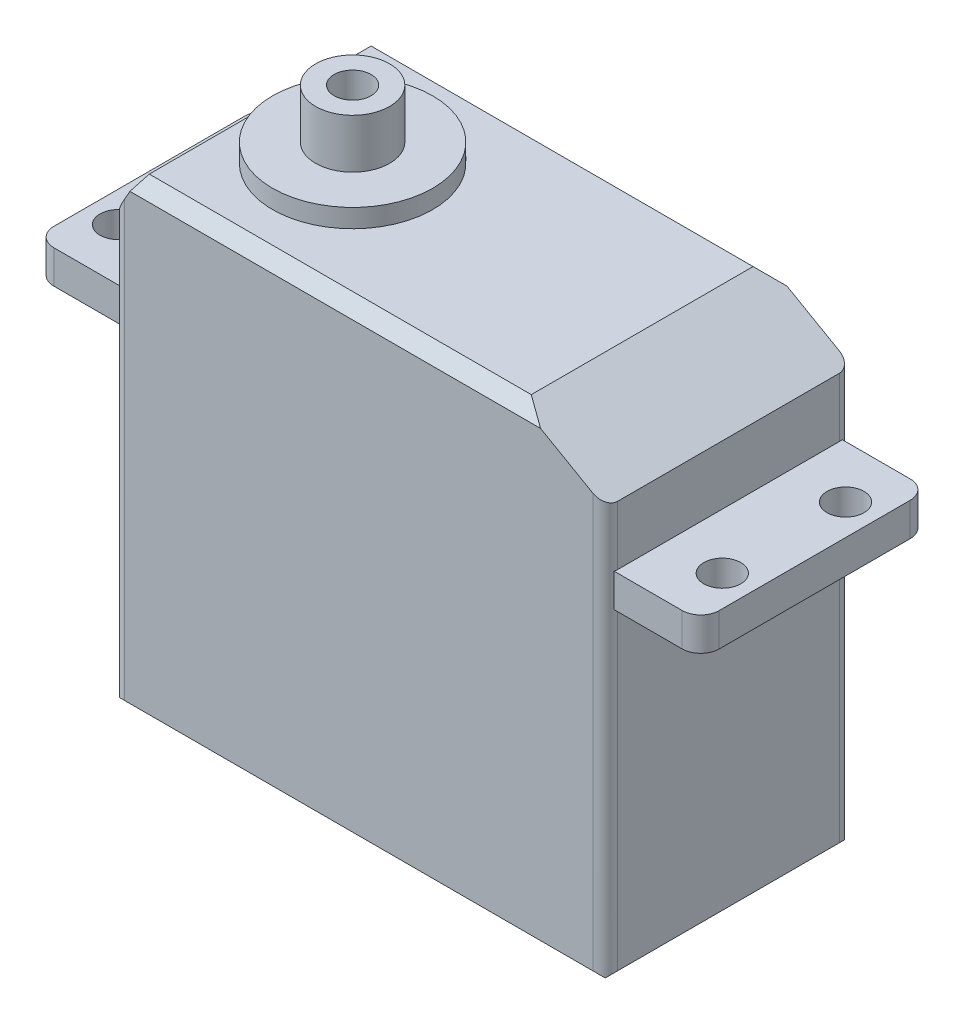
SolidWorks part; units mm, degrees
ref_plane "前视基准面" through (0, 0, 0) normal (0, 0, 1) x (1, 0, 0)
ref_plane "上视基准面" through (0, 0, 0) normal (0, 1, 0) x (1, 0, 0)
ref_plane "右视基准面" through (0, 0, 0) normal (1, 0, 0) x (0, 0, -1)
sketch "草图1" plane through (0, 0, 0) normal (0, 0, 1) x (1, 0, 0)
  line L1 (0, 0) -> (40, 0)
  line L2 (0, 0) -> (0, 38)
  line L3 (0, 38) -> (40, 38)
  line L4 (40, 0) -> (40, 38)
  dimension "D1" = 40
  dimension "D2" = 38
extrude "凸台-拉伸1" add sketch "草图1" along normal blind 20
sketch "草图2" plane through (0, 0, 0) normal (-1, 0, 0) x (0, 0, 1)
  line L0 (20, 0) -> (0, 0) construction
  line L1 (0.75, 29.2) -> (19.25, 29.2)
  line L2 (0.75, 29.2) -> (0.75, 26.5)
  line L3 (0.75, 26.5) -> (19.25, 26.5)
  line L4 (19.25, 29.2) -> (19.25, 26.5)
  line L5 (20, 38) -> (0, 38) construction
  point P8 (10, 38)
  point P9 (10, 29.2)
  dimension "D1" = 18.5
  dimension "D2" = 26.5
  dimension "D3" = 2.7
extrude "凸台-拉伸2" add sketch "草图2" along normal blind 7
sketch "草图3" plane through (40, 0, 0) normal (1, 0, 0) x (0, 0, -1)
  line L4 (-0.75, 26.5) -> (-0.75, 29.2)
  line L5 (-19.25, 26.5) -> (-0.75, 26.5)
  line L6 (-19.25, 29.2) -> (-19.25, 26.5)
  line L7 (-0.75, 29.2) -> (-19.25, 29.2)
  line L8 (-0.75, 26.5) -> (-0.75, 29.2)
  line L9 (-19.25, 26.5) -> (-0.75, 26.5)
  line L10 (-19.25, 29.2) -> (-19.25, 26.5)
  line L11 (-0.75, 29.2) -> (-19.25, 29.2)
  dimension "D1" = 0
extrude "凸台-拉伸3" add sketch "草图3" along normal blind 7
sketch "草图4" plane through (0, 29.2, 0) normal (0, 1, 0) x (1, 0, 0)
  line L0 (-4.5, -15) -> (-4.5, -5) construction
  line L1 (-4.5, -5) -> (44.5, -5) construction
  line L2 (40, 0) -> (0, 0) construction
  line L3 (-7, -19.25) -> (-7, -0.75) construction
  circle A0 centre (-4.5, -5) radius 1.5
  circle A1 centre (44.5, -5) radius 1.5
  circle A2 centre (-4.5, -15) radius 1.5
  circle A3 centre (44.5, -15) radius 1.5
  point P10 (20, 0)
  point P11 (20, -5)
  point P14 (-7, -10)
  point P15 (-4.5, -10)
  point P16 (0, 0)
  point P17 (0, 0)
  dimension "D3" = 3
  dimension "D4" = 3
  dimension "D5" = 3
  dimension "D6" = 3
  dimension "D1" = 49
  dimension "D2" = 10
extrude "切除-拉伸1" cut sketch "草图4" against normal blind 7
chamfer "倒角1" distance 1 angle 45 4 edges at (0, 0, 10) (20, 0, 20) (40, 0, 10) (20, 0, 0)
chamfer "倒角2" distance 2 distance2 3.5 1 edges at (0, 38, 10) first distance on face at (20, 38, 10)
chamfer "倒角3" distance 4 distance2 7 1 edges at (40, 38, 10) first distance on face at (40, 19.5, 10)
chamfer "倒角4" distance 1 angle 45 2 edges at (17.5, 38, 0) (17.5, 38, 20)
sketch "草图5" plane through (0, 38, 0) normal (0, 1, 0) x (1, 0, 0)
  line L0 (0, -19.25) -> (0, -0.75) construction
  line L1 (2, -1) -> (2, -19) construction
  circle A0 centre (9.5, -10) radius 6.5
  point P6 (2, -10)
  dimension "D2" = 13
  dimension "D1" = 9.5
extrude "凸台-拉伸4" add sketch "草图5" along normal blind 1.5
sketch "草图6" plane through (0, 39.5, 0) normal (0, 1, 0) x (1, 0, 0)
  circle A0 centre (9.5, -10) radius 3
  circle A1 centre (9.5, -10) radius 1.5
  dimension "D1" = 6
  dimension "D2" = 3
extrude "凸台-拉伸5" add sketch "草图6" along normal blind 4
fillet "圆角1" radius 1.5 4 edges at (47, 27.85, 0.75) (47, 27.85, 19.25) (-7, 27.85, 0.75) (-7, 27.85, 19.25)
fillet "圆角2" radius 1 4 edges at (0, 17.75, 20) (0, 17.75, 0) (40, 17.5, 0) (40, 17.5, 20)
